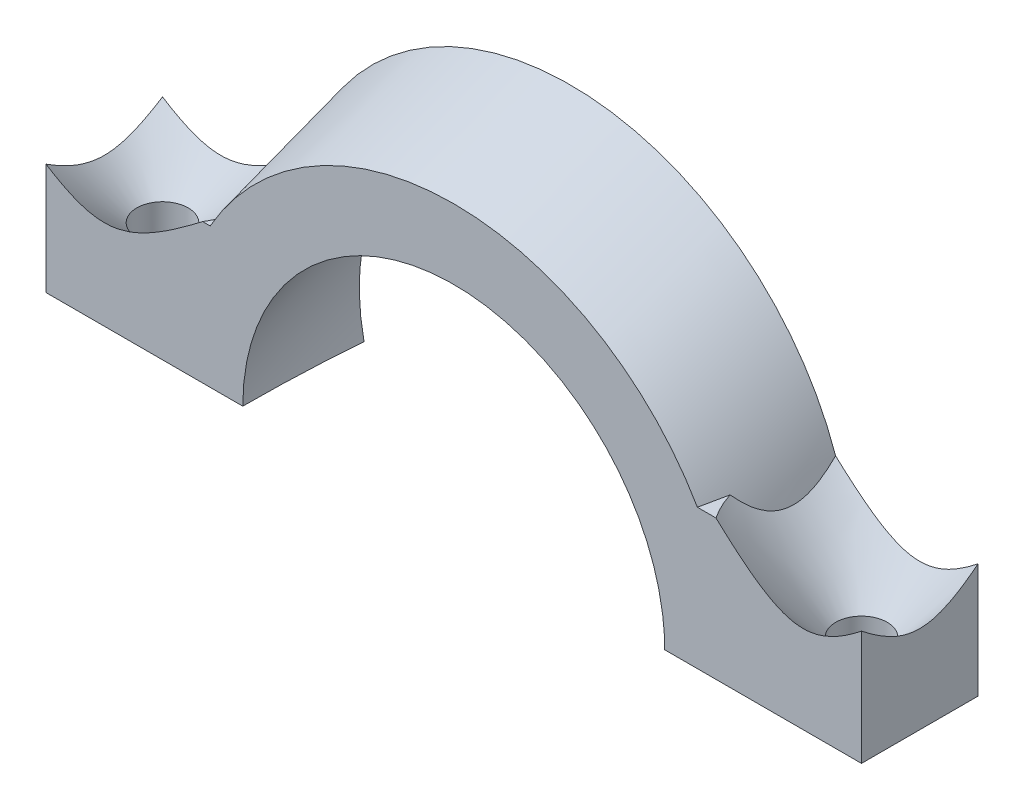
SolidWorks part; units mm, degrees
note: The reader was unsure of these and kept them because the rebuilt part matched: shared geometry of "Sketch2<3>", "Sketch2<4>", "Sketch5<4>".
ref_plane "Front Plane" through (0, 0, 0) normal (0, 0, 1) x (1, 0, 0)
ref_plane "Top Plane" through (0, 0, 0) normal (0, 1, 0) x (1, 0, 0)
ref_plane "Right Plane" through (0, 0, 0) normal (1, 0, 0) x (0, 0, -1)
sketch "Sketch1" plane through (0, 0, 0) normal (0, 1, 0) x (1, 0, 0)
  line L1 (22.225, -47.625) -> (-22.225, -47.625)
  line L2 (22.225, -47.625) -> (22.225, 47.625)
  line L3 (22.225, 47.625) -> (-22.225, 47.625)
  line L4 (-22.225, -47.625) -> (-22.225, 47.625)
  line L5 (22.225, -47.625) -> (-22.225, 47.625) construction
  line L6 (22.225, 47.625) -> (-22.225, -47.625) construction
  point P0 (0, 0)
  dimension "D1" = 95.25
  dimension "D2" = 44.45
extrude "Boss-Extrude1" add sketch "Sketch1" along normal blind 3.175
sketch "Sketch2" plane through (0, 0, 0) normal (1, 0, 0) x (0, 0, -1)
  line L3 (-47.625, 3.175) -> (-47.625, 0) construction
  line L4 (-36.83, 3.175) -> (-36.83, 19.05)
  line L5 (-24.1873, 28.0503) -> (47.625, 3.175)
  line L6 (-47.625, 3.175) -> (47.625, 3.175)
  line L7 (-47.625, 3.175) -> (-35.5269, 23.859)
  line L8 (-17.78, 3.175) -> (-17.78, 19.05)
  circle A0 centre (-27.305, 19.05) radius 4
  arc A2 (-35.5269, 23.859) -> (-24.1873, 28.0503) centre (-27.305, 19.05) cw
  arc A3 (-17.78, 19.05) -> (-36.83, 19.05) centre (-27.305, 19.05) ccw
  point P6 (-47.625, 1.5875)
  dimension "D1" = 8
  dimension "D6" = 19.05
  dimension "D2" = 20.32
  dimension "D3" = 19.05
extrude "Boss-Extrude2" add sketch "Sketch2" along normal mid plane 44.45
extrude "Cut-Extrude1" cut sketch "Sketch2<3>" against normal mid plane 31.75 contours A3 L7 L6 L4 | A3 L8 L6 L5
sketch "Sketch2<3>" plane through (0, 0, 0) normal (1, 0, 0) x (0, 0, -1) same geometry as "Sketch2"
extrude "Cut-Extrude2" cut sketch "Sketch2<4>" against normal mid plane 16.51
sketch "Sketch2<4>" plane through (0, 0, 0) normal (1, 0, 0) x (0, 0, -1) same geometry as "Sketch2"
sketch "Sketch3" plane through (0, 3.175, 0) normal (0, 1, 0) x (1, 0, 0)
  line L0 (-15.875, 0) -> (15.875, 0) construction
  line L5 (-15.875, -24.1873) -> (-15.875, 47.625) construction
  line L6 (15.875, -17.78) -> (15.875, 47.625) construction
  line L8 (-6.35, 43.005) -> (6.35, 43.005)
  line L9 (-6.35, 43.005) -> (-6.35, 37.005)
  line L10 (-6.35, 37.005) -> (6.35, 37.005)
  line L11 (6.35, 43.005) -> (6.35, 37.005)
  line L12 (-6.35, 43.005) -> (6.35, 37.005) construction
  line L13 (6.35, 43.005) -> (-6.35, 37.005) construction
  line L14 (-15.875, 47.625) -> (15.875, 47.625) construction
  line L15 (-6.35, -37.005) -> (6.35, -37.005)
  line L16 (6.35, -43.005) -> (6.35, -37.005)
  line L17 (-6.35, -43.005) -> (6.35, -43.005)
  line L18 (-6.35, -43.005) -> (-6.35, -37.005)
  point P11 (0, 37.005)
  point P12 (0, 40.005)
  dimension "D1" = 12.7
  dimension "D2" = 6
  dimension "D3" = 7.62
extrude "Cut-Extrude3" cut sketch "Sketch3" against normal through all
sketch "Sketch4" plane through (0, 3.175, 0) normal (0, 1, 0) x (1, 0, 0)
  line L0 (-22.225, -24.1873) -> (-22.225, 47.625) construction
  line L1 (-22.225, 32.385) -> (22.225, 32.385)
  line L2 (-22.225, 32.385) -> (-22.225, 26.035)
  line L3 (-22.225, 26.035) -> (22.225, 26.035)
  line L4 (22.225, 32.385) -> (22.225, 26.035)
  line L5 (22.225, -24.1873) -> (22.225, 47.625) construction
  line L6 (-6.35, 43.005) -> (-6.35, 37.005) construction
  point P10 (-6.35, 40.005)
  dimension "D1" = 7.62
  dimension "D2" = 6.35
extrude "Boss-Extrude3" add sketch "Sketch4" along normal blind 55.88
ref_plane "Plane1" through (0, 0, 0) normal (1, 0, 0) x (0, 0, -1)
sketch "Sketch5" plane through (0, 0, 0) normal (1, 0, 0) x (0, 0, -1)
  line L0 (-27.305, 19.05) -> (48.895, 19.05) construction
  line L1 (-27.305, 19.05) -> (43.8338, 46.3576)
  dimension "D1" = 76.2
  dimension "D2" = 76.2
  dimension "D3" = 21
sketch "Sketch6" plane through (0, 0, -26.035) normal (0, 0, 1) x (1, 0, 0)
  circle A0 centre (0, 39.5253) radius 11.5
  point P0 (0, 39.5253)
  dimension "D1" = 23
sweep "Cut-Sweep1" cut profiles "Sketch6" path "Sketch5"
sketch "Sketch10" plane through (0, 0, -26.035) normal (0, 0, 1) x (1, 0, 0)
  line L1 (-22.225, 59.055) -> (-22.225, 10.6536) construction
  line L2 (22.225, 59.055) -> (22.225, 10.6536) construction
  line L4 (-22.225, 39.5253) -> (-15.31, 39.5253)
  line L5 (15.31, 39.5253) -> (22.225, 39.5253)
  line L6 (-22.225, 39.5253) -> (-22.225, 59.055)
  line L7 (-22.225, 59.055) -> (22.225, 59.055)
  line L8 (22.225, 59.055) -> (22.225, 39.5253)
  circle A3 centre (0, 39.5253) radius 11.5 construction
  arc A4 (15.31, 39.5253) -> (-15.31, 39.5253) centre (0, 39.5253) ccw
  dimension "D2" = 3.81
sweep "Cut-Sweep4" cut profiles "Sketch10" path "Sketch5<4>"
sketch "Sketch5<4>" plane through (0, 0, 0) normal (1, 0, 0) x (0, 0, -1) same geometry as "Sketch5"
sketch "Sketch11" plane through (0, 0, -26.035) normal (0, 0, 1) x (1, 0, 0)
  line L0 (22.225, 39.5253) -> (22.225, 10.6536) construction
  line L1 (-22.225, 39.5253) -> (22.225, 39.5253)
  line L2 (-22.225, 39.5253) -> (-22.225, 47.1453)
  line L3 (-22.225, 47.1453) -> (22.225, 47.1453)
  line L4 (22.225, 39.5253) -> (22.225, 47.1453)
  arc A0 (15.31, 39.5253) -> (13.279, 47.1453) centre (0, 39.5253) ccw
  arc A1 (-13.279, 47.1453) -> (-15.31, 39.5253) centre (0, 39.5253) ccw
  line M6 (-15.31, 39.5253) -> (-22.225, 39.5253)
  line M14 (22.225, 39.5253) -> (15.31, 39.5253)
  arc M15 (15.31, 39.5253) -> (-15.31, 39.5253) centre (0, 39.5253) ccw
  dimension "D1" = 7.62
extrude "Boss-Extrude4" add sketch "Sketch11" against normal blind 6.35 contours L3 L2 M6 M15 | L4 L3 M14 M15
sketch "Sketch12" plane through (0, 47.1453, 0) normal (0, 1, 0) x (1, 0, 0)
  line L0 (-22.225, 32.385) -> (-22.225, 26.035) construction
  line L1 (-22.225, 32.385) -> (-15.875, 32.385) construction
  line L2 (0, 0) -> (0, 50.8)
  circle A0 centre (-19.05, 29.21) radius 1.4
  circle A1 centre (19.05, 29.21) radius 1.4
  dimension "D3" = 2.8
  dimension "D1" = 3.175
  dimension "D2" = 3.175
  dimension "D4" = 50.8
extrude "Cut-Extrude4" cut sketch "Sketch12" against normal blind 18.75 contours A0 | A1
chamfer "Chamfer1" distance 4.83 distance2 4.32 2 edges at (19.05, 47.1453, -27.81) (-19.05, 47.1453, -27.81) first distance on face at (19.05, 28.3953, -27.81) first distance on face at (-19.05, 47.1453, -27.81)
sketch "Sketch13" plane through (0, 0, -26.035) normal (0, 0, 1) x (1, 0, 0)
  line L1 (-35.3917, 39.5253) -> (31.1619, 39.5253)
  line L2 (-35.3917, 39.5253) -> (-35.3917, -4.1635)
  line L3 (-35.3917, -4.1635) -> (31.1619, -4.1635)
  line L4 (31.1619, 39.5253) -> (31.1619, -4.1635)
extrude "Cut-Extrude5" cut sketch "Sketch13" against normal through all both and the other way through all
